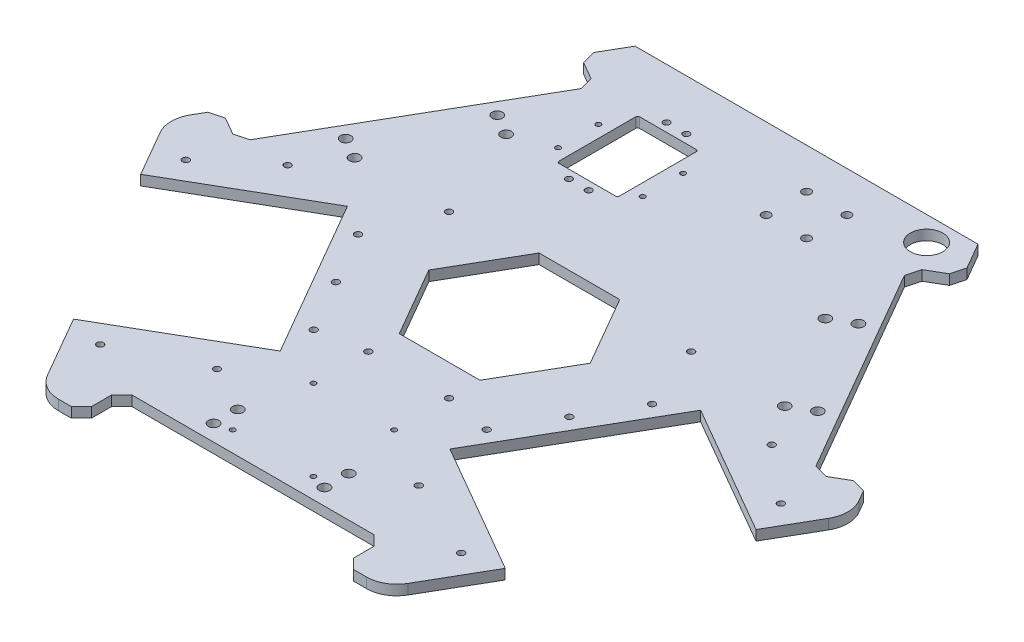
SolidWorks part; units mm, degrees
material "5052-O"
ref_plane "前基準面" through (0, 0, 0) normal (0, 0, 1) x (1, 0, 0)
ref_plane "上基準面" through (0, 0, 0) normal (0, 1, 0) x (1, 0, 0)
ref_plane "右基準面" through (0, 0, 0) normal (1, 0, 0) x (0, 0, -1)
sketch "草圖1" plane through (0, 0, 0) normal (0, 1, 0) x (1, 0, 0)
  line L1 (85, 147.2243) -> (-85, 147.2243)
  line L2 (-85, 147.2243) -> (-170, 0)
  line L3 (-170, 0) -> (-85, -147.2243)
  line L4 (-85, -147.2243) -> (85, -147.2243)
  line L5 (85, -147.2243) -> (170, 0)
  line L6 (170, 0) -> (85, 147.2243)
  circle A0 centre (0, 0) radius 147.2243 construction
  dimension "D1" = 170
extrude "填料-伸長1" add sketch "草圖1" along normal blind 5
ref_axis "基準軸1" through (0, -0.25, 0) along (0, 1, 0)
sketch "草圖46" plane through (0, 5, 0) normal (0, 1, 0) x (1, 0, 0)
  line L0 (-65, -147.2243) -> (65, -147.2243)
  line L1 (-65, -147.2243) -> (-65, -127.2243)
  line L2 (65, -147.2243) -> (65, -127.2243)
  line L3 (-65, -127.2243) -> (65, -127.2243)
  line L4 (-85, -147.2243) -> (85, -147.2243) construction
  point P6 (0, -147.2243)
  point P7 (0, -147.2243)
  dimension "D1" = 20
  dimension "D2" = 130
extrude "除料-伸長31" cut sketch "草圖46" against normal up to next
sketch "草圖8" plane through (0, 5, 0) normal (0, 1, 0) x (1, 0, 0)
  line L0 (65, -127.2243) -> (-65, -127.2243) construction
  line L2 (-27.5, -107.2243) -> (27.5, -107.2243) construction
  line L3 (-27.5, -107.2243) -> (-27.5, -119.2243) construction
  line L4 (-27.5, -119.2243) -> (27.5, -119.2243) construction
  line L5 (27.5, -107.2243) -> (27.5, -119.2243) construction
  circle A0 centre (-27.5, -119.2243) radius 2.6
  circle A1 centre (27.5, -119.2243) radius 2.6
  circle A2 centre (-27.5, -107.2243) radius 2.6
  circle A3 centre (27.5, -107.2243) radius 2.6
  point P7 (0, -119.2243)
  point P14 (0, -127.2243)
  dimension "D3" = 5.2
  dimension "D1" = 55
  dimension "D2" = 12
  dimension "D4" = 8
extrude "除料-伸長6" cut sketch "草圖8" against normal through all
pattern_circular "環狀複製排列1" count 3 over 360 about axis through (0, -0.25, 0) along (0, 1, 0) of "除料-伸長6", "除料-伸長31"
chamfer "導角1" distance 5 angle 45 12 edges at (65, 2.5, 127.2243) (65, 2.5, 147.2243) (-65, 2.5, 147.2243) (-65, 2.5, 127.2243) (77.6795, 2.5, -119.9038) (95, 2.5, -129.9038) (160, 2.5, -17.3205) (142.6795, 2.5, -7.3205) (-160, 2.5, -17.3205) (-142.6795, 2.5, -7.3205) (-77.6795, 2.5, -119.9038) (-95, 2.5, -129.9038)
sketch "草圖5" plane through (0, 5, 0) normal (0, 1, 0) x (1, 0, 0)
  line L0 (-152.5, -30.3109) -> (-107, -109.1192)
  line L1 (-152.5, -30.3109) -> (-87.5481, 7.1891)
  line L2 (-107, -109.1192) -> (-42.0481, -71.6192)
  line L3 (-87.5481, 7.1891) -> (-42.0481, -71.6192)
  line L4 (-170, 0) -> (-85, -147.2243) construction
  dimension "D1" = 75
  dimension "D2" = 91
  dimension "35" = 35
extrude "除料-伸長4" cut sketch "草圖5" against normal through all
sketch "草圖9" plane through (0, 5, 0) normal (0, 1, 0) x (1, 0, 0)
  line L0 (-64.7981, -32.215) -> (-118.4917, -63.215) construction
  line L1 (-42.0481, -71.6192) -> (-87.5481, 7.1891) construction
  line L2 (-118.4917, -63.215) -> (-89.4917, -113.4445) construction
  line L3 (-118.4917, -63.215) -> (-147.4917, -12.9856) construction
  circle A0 centre (-89.4917, -113.4445) radius 1.65
  circle A1 centre (-147.4917, -12.9856) radius 1.65
  dimension "D2" = 3.3
  dimension "D1" = 58
  dimension "D3" = 62
  dimension "D4" = 58
extrude "除料-伸長7" cut sketch "草圖9" against normal through all
mirror "鏡射1" about plane through (0, 0, 0) normal (1, 0, 0) of "除料-伸長4", "除料-伸長7"
fillet "圓角1" radius 15 4 edges at (170, 2.5, 0) (85, 2.5, 147.2243) (-170, 2.5, 0) (-85, 2.5, 147.2243)
sketch "草圖36" plane through (0, 5, 0) normal (0, 1, 0) x (1, 0, 0)
  line L0 (-72.8699, -2.2343) -> (-57.8699, -28.215) construction
  line L1 (-42.0481, -71.6192) -> (-87.5481, 7.1891) construction
  line L2 (-42.8699, -54.1958) -> (-57.8699, -28.215) construction
  line L3 (-57.8699, -28.215) -> (-64.7981, -32.215) construction
  circle A0 centre (-57.8699, -28.215) radius 1.25
  circle A1 centre (-42.8699, -54.1958) radius 1.25
  circle A2 centre (-72.8699, -2.2343) radius 1.25
  point P7 (-50.3699, -41.2054)
  point P10 (-64.7981, -32.215)
  dimension "D3" = 2.5
  dimension "D1" = 30
  dimension "D2" = 30
  dimension "D4" = 8
hole_wizard "M4x0.7 螺紋孔4" positions "草圖40" profile "草圖41" tap size "M4x0.7" standard "Ansi Metric" end condition through all
sketch "草圖40" plane through (0, 5, 0) normal (0, 1, 0) x (1, 0, 0)
  point P0 (-72.8699, -2.2343)
  point P3 (-57.8699, -28.215)
  point P6 (-42.8699, -54.1958)
sketch "草圖41" plane through (-72.8699, 5, 2.2343) normal (1, 0, 0) x (0, 0, 1)
  line L0 (0, 0) -> (0, 5)
  line L1 (0, 5) -> (1.65, 5)
  line L2 (1.65, 5) -> (1.65, 0)
  line L5 (1.65, 0) -> (0, 0)
  line L11 (0, -6.35) -> (0, 107.95) construction
  dimension "貫穿螺孔鑽直徑" = 3.3
  dimension "貫穿螺孔鑽深度" = 5
cosmetic thread "鑽孔螺紋1" parameters "D1"=10, "D2"=4.3
cosmetic thread "鑽孔螺紋2" parameters "D1"=10, "D2"=4.3
cosmetic thread "鑽孔螺紋3" parameters "D1"=10, "D2"=4.3
mirror "鏡射2" about plane through (0, 0, 0) normal (1, 0, 0) of "M4x0.7 螺紋孔4"
sketch "草圖51" plane through (0, 5, 0) normal (0, 1, 0) x (1, 0, 0)
  line L0 (85, 147.2243) -> (-85, 147.2243) construction
  line L1 (20, 34.641) -> (-20, 34.641)
  line L2 (-20, 34.641) -> (-40, 0)
  line L3 (-40, 0) -> (-20, -34.641)
  line L4 (-20, -34.641) -> (20, -34.641)
  line L5 (20, -34.641) -> (40, 0)
  line L6 (40, 0) -> (20, 34.641)
  circle A0 centre (0, 0) radius 34.641 construction
  dimension "D1" = 40
extrude "除料-伸長35" cut sketch "草圖51" against normal up to next
sketch "草圖53" plane through (0, 5, 0) normal (0, 1, 0) x (1, 0, 0)
  line L0 (85, 147.2243) -> (-85, 147.2243) construction
  line L1 (20, 127.2243) -> (40, 127.2243) construction
  line L2 (20, 127.2243) -> (20, 107.2243) construction
  line L3 (20, 107.2243) -> (40, 107.2243) construction
  line L4 (40, 127.2243) -> (40, 107.2243) construction
  line L5 (20, 127.2243) -> (-85, 127.2243) construction
  line L6 (-85, 127.2243) -> (-85, 147.2243) construction
  circle A0 centre (20, 127.2243) radius 2.1
  dimension "D4" = 4.2
  dimension "D1" = 20
  dimension "D2" = 20
  dimension "D3" = 20
  dimension "D5" = 90
  dimension "D6" = 105
extrude "除料-伸長37" cut sketch "草圖53" against normal up to next
pattern_linear "直線複製排列1" count 2 spacing 20 along (1, 0, 0) count 2 spacing 20 along (0, 0, 1) of "除料-伸長37"
sketch "草圖54" plane through (0, 5, 0) normal (0, 1, 0) x (1, 0, 0)
  circle A0 centre (71.5, 135.2243) radius 8.05
  circle A1 centre (40, 127.2243) radius 2.1 construction
  dimension "D1" = 16.1
  dimension "D2" = 31.5
  dimension "D3" = 8
extrude "除料-伸長38" cut sketch "草圖54" against normal up to next
sketch "草圖56" plane through (0, 0, 0) normal (0, -1, 0) x (-1, 0, 0)
  line L0 (-85, 147.2243) -> (85, 147.2243) construction
  line L2 (34.6, 73.8243) -> (34.6, 122.2243) construction
  line L3 (34.6, 122.2243) -> (44.4, 122.2243) construction
  line L4 (44.4, 122.2243) -> (44.4, 73.8243) construction
  circle A0 centre (34.6, 122.2243) radius 1.6
  circle A1 centre (44.4, 122.2243) radius 1.6
  circle A2 centre (44.4, 73.8243) radius 1.6
  circle A3 centre (34.6, 73.8243) radius 1.6
  point P2 (0, 147.2243)
  point P5 (39.5, 122.2243)
  dimension "D1" = 3.2
  dimension "D2" = 25
  dimension "D3" = 39.5
  dimension "D6" = 48.4
  dimension "D7" = 9.8
  dimension "D4" = 2
  dimension "D5" = 2
extrude "除料-伸長40" cut sketch "草圖56" against normal blind 10 contours A3 | A2 | A1 | A0
sketch "草圖55" plane through (0, 5, 0) normal (0, 1, 0) x (1, 0, 0)
  line L1 (-24.5, 118.0243) -> (-54.5, 118.0243)
  line L2 (-24.5, 118.0243) -> (-24.5, 78.0243)
  line L3 (-24.5, 78.0243) -> (-54.5, 78.0243)
  line L4 (-54.5, 118.0243) -> (-54.5, 78.0243)
  line L5 (85, 147.2243) -> (-85, 147.2243) construction
  circle A2 centre (-34.6, 122.2243) radius 1.6 construction
  point P6 (-39.5, 118.0243)
  point P9 (0, 147.2243)
  dimension "D3" = 4.2
  dimension "D1" = 40
  dimension "D2" = 30
  dimension "D4" = 39.5
extrude "除料-伸長39" cut sketch "草圖55" against normal blind 10 contours L2 L1 L4 L3
fillet "圓角2" radius 1 4 edges at (-54.5, 2.5, -78.0243) (-24.5, 2.5, -78.0243) (-24.5, 2.5, -118.0243) (-54.5, 2.5, -118.0243)
hole_wizard "M3x0.5 螺紋孔1" positions "草圖58" profile "草圖59" tap size "M3x0.5" standard "Ansi Metric"
sketch "草圖58" plane through (0, 5, 0) normal (0, 1, 0) x (1, 0, 0)
  line L1 (-60.5, 104.5243) -> (-18.5, 104.5243) construction
  line L2 (-60.5, 104.5243) -> (-60.5, 84.5243) construction
  line L3 (-60.5, 84.5243) -> (-18.5, 84.5243) construction
  line L4 (-18.5, 104.5243) -> (-18.5, 84.5243) construction
  line L5 (-25.5, 118.0243) -> (-53.5, 118.0243) construction
  point P0 (-60.5, 104.5243)
  point P2 (-60.5, 84.5243)
  point P4 (-18.5, 84.5243)
  point P6 (-18.5, 104.5243)
  point P110 (-39.5, 104.5243)
  point P113 (-39.5, 118.0243)
  dimension "D1" = 20
  dimension "D2" = 42
  dimension "D3" = 13.5
sketch "草圖59" plane through (-60.5, 5, -104.5243) normal (1, 0, 0) x (0, 0, 1)
  line L0 (0, 0) -> (0, 9.2511)
  line L1 (0, 9.2511) -> (1.25, 8.5)
  line L2 (1.25, 8.5) -> (1.25, 0)
  line L5 (1.25, 0) -> (0, 0)
  line L10 (0, 9.2511) -> (-1.25, 8.5) construction
  line L11 (0, -6.35) -> (0, 107.95) construction
  dimension "螺孔鑽直徑" = 2.5
  dimension "螺孔鑽深度" = 8.5
  dimension "導頭角度" = 118
cosmetic thread "鑽孔螺紋4" parameters "D1"=5, "D2"=3
cosmetic thread "鑽孔螺紋5" parameters "D1"=5, "D2"=3
cosmetic thread "鑽孔螺紋6" parameters "D1"=5, "D2"=3
cosmetic thread "鑽孔螺紋7" parameters "D1"=5, "D2"=3
hole_wizard "M4x0.7 螺紋孔5" positions "草圖60" profile "草圖61" tap size "M4x0.7" standard "Ansi Metric"
sketch "草圖60" plane through (0, 5, 0) normal (0, 1, 0) x (1, 0, 0)
  point P0 (-50, -95)
  point P1 (-120, 10)
  point P14 (-60, 30)
  point P16 (-20, -50)
  dimension "D1" = 120
  dimension "D2" = 95
  dimension "D3" = 50
  dimension "D4" = 10
  dimension "D5" = 50
  dimension "D6" = 20
  dimension "D7" = 60
  dimension "D8" = 30
sketch "草圖61" plane through (-50, 5, 95) normal (1, 0, 0) x (0, 0, 1)
  line L0 (0, 0) -> (0, 12.4914)
  line L1 (0, 12.4914) -> (1.65, 11.5)
  line L2 (1.65, 11.5) -> (1.65, 0)
  line L5 (1.65, 0) -> (0, 0)
  line L10 (0, 12.4914) -> (-1.65, 11.5) construction
  line L11 (0, -6.35) -> (0, 107.95) construction
  dimension "螺孔鑽直徑" = 3.3
  dimension "螺孔鑽深度" = 11.5
  dimension "導頭角度" = 118
cosmetic thread "鑽孔螺紋8" parameters "D1"=5, "D2"=4
cosmetic thread "鑽孔螺紋9" parameters "D1"=5, "D2"=4
cosmetic thread "鑽孔螺紋16" parameters "D1"=5, "D2"=4
cosmetic thread "鑽孔螺紋17" parameters "D1"=5, "D2"=4
mirror "鏡射3" about plane through (0, 0, 0) normal (1, 0, 0) of "M4x0.7 螺紋孔5"
hole_wizard "M3x0.5 螺紋孔2" positions "草圖62" profile "草圖63" tap size "M3x0.5" standard "Ansi Metric"
sketch "草圖62" plane through (0, 5, 0) normal (0, 1, 0) x (1, 0, 0)
  line L1 (-20, -77.2243) -> (20, -77.2243) construction
  line L2 (-20, -77.2243) -> (-20, -117.2243) construction
  line L3 (-20, -117.2243) -> (20, -117.2243) construction
  line L4 (20, -77.2243) -> (20, -117.2243) construction
  line L5 (60, -127.2243) -> (-60, -127.2243) construction
  point P0 (-20, -77.2243)
  point P2 (-20, -117.2243)
  point P4 (20, -117.2243)
  point P6 (20, -77.2243)
  point P51 (0, -77.2243)
  dimension "D1" = 40
  dimension "D2" = 40
  dimension "D3" = 10
sketch "草圖63" plane through (-20, 5, 77.2243) normal (1, 0, 0) x (0, 0, 1)
  line L0 (0, 0) -> (0, 9.2511)
  line L1 (0, 9.2511) -> (1.25, 8.5)
  line L2 (1.25, 8.5) -> (1.25, 0)
  line L5 (1.25, 0) -> (0, 0)
  line L10 (0, 9.2511) -> (-1.25, 8.5) construction
  line L11 (0, -6.35) -> (0, 107.95) construction
  dimension "螺孔鑽直徑" = 2.5
  dimension "螺孔鑽深度" = 8.5
  dimension "導頭角度" = 118
cosmetic thread "鑽孔螺紋18" parameters "D1"=5, "D2"=3
cosmetic thread "鑽孔螺紋19" parameters "D1"=5, "D2"=3
cosmetic thread "鑽孔螺紋20" parameters "D1"=5, "D2"=3
cosmetic thread "鑽孔螺紋21" parameters "D1"=5, "D2"=3
